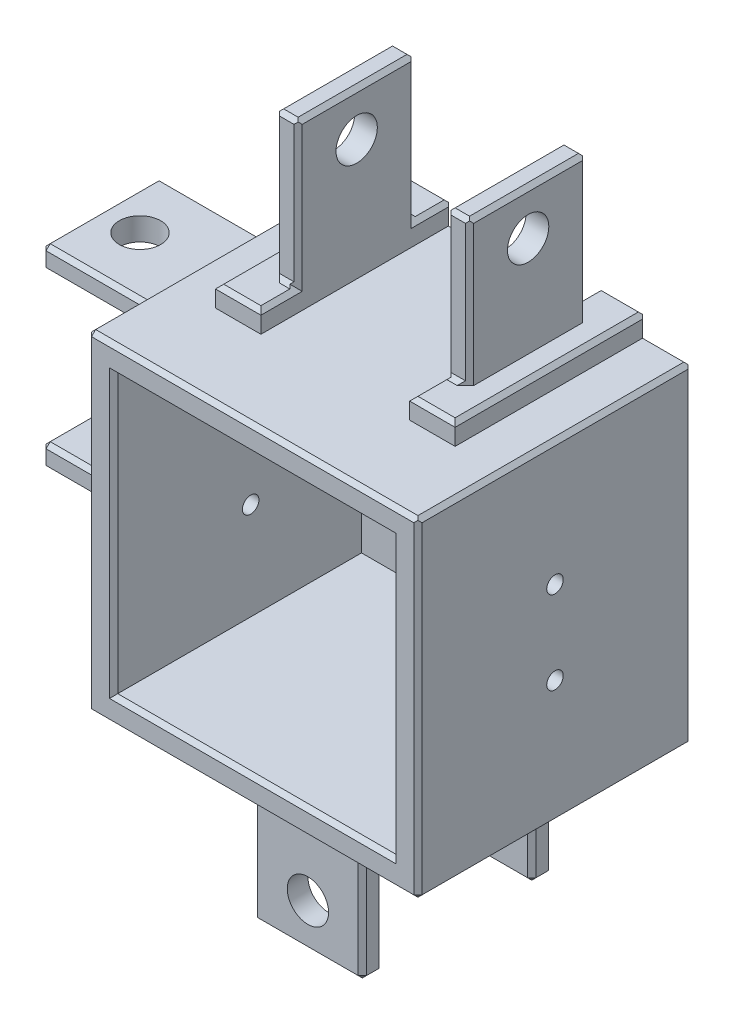
SolidWorks part; units mm, degrees
ref_plane "Alzado" through (0, 0, 0) normal (0, 0, 1) x (1, 0, 0)
ref_plane "Planta" through (0, 0, 0) normal (0, 1, 0) x (1, 0, 0)
ref_plane "Vista lateral" through (0, 0, 0) normal (1, 0, 0) x (0, 0, -1)
sketch "Croquis2" plane through (0, 0, 0) normal (0, 0, 1) x (1, 0, 0)
  line L0 (-30.0752, 21.0526) -> (-30.0752, -58.9474)
  line L1 (-30.0752, -58.9474) -> (49.9248, -58.9474)
  line L2 (49.9248, -58.9474) -> (49.9248, 21.0526)
  line L3 (49.9248, 21.0526) -> (-30.0752, 21.0526)
  dimension "D1" = 80
  dimension "D2" = 80
extrude "Saliente-Extruir1" add sketch "Croquis2" along normal blind 6.35
sketch "Croquis4" plane through (0, 0, 6.35) normal (0, 0, 1) x (1, 0, 0)
  line L0 (-30.0752, 21.0526) -> (49.9248, -58.9474) construction
  line L1 (49.9248, 21.0526) -> (-30.0752, 21.0526) construction
  line L2 (43.5748, -52.5974) -> (-23.7252, -52.5974)
  line L3 (43.5748, -52.5974) -> (43.5748, 14.7026)
  line L4 (43.5748, 14.7026) -> (-23.7252, 14.7026)
  line L5 (-23.7252, -52.5974) -> (-23.7252, 14.7026)
  line L6 (43.5748, -52.5974) -> (-23.7252, 14.7026) construction
  line L7 (43.5748, 14.7026) -> (-23.7252, -52.5974) construction
  line L8 (-30.0752, 21.0526) -> (-30.0752, -58.9474) construction
  line L10 (49.9248, -58.9474) -> (-30.0752, -58.9474)
  line L11 (49.9248, -58.9474) -> (49.9248, 21.0526)
  line L12 (49.9248, 21.0526) -> (-30.0752, 21.0526)
  line L13 (-30.0752, -58.9474) -> (-30.0752, 21.0526)
  line L14 (49.9248, -58.9474) -> (-30.0752, 21.0526) construction
  line L15 (49.9248, 21.0526) -> (-30.0752, -58.9474) construction
  point P4 (9.9248, -18.9474)
  point P13 (9.9248, -18.9474)
  dimension "D1" = 6.35
  dimension "D2" = 6.35
extrude "Saliente-Extruir2" add sketch "Croquis4" along normal blind 60
sketch "Croquis5" plane through (0, 0, 6.35) normal (0, 0, 1) x (1, 0, 0)
  line L0 (-23.7252, -52.5974) -> (43.5748, 14.7026) construction
  line L2 (-23.7252, 14.7026) -> (43.5748, -52.5974) construction
  circle A0 centre (9.9248, -18.9474) radius 30
  dimension "D1" = 60
extrude "Cortar-Extruir1" cut sketch "Croquis5" against normal blind 40
sketch "Croquis6" plane through (0, 21.0526, 0) normal (0, 1, 0) x (1, 0, 0)
  line L28 (27.9248, 0) -> (38.9248, 0)
  line L29 (-13.5752, -9) -> (-13.5752, -37.35)
  line L30 (-8.0752, -37.35) -> (-13.5752, -37.35)
  line L31 (-8.0752, -9) -> (-8.0752, -37.35)
  line L32 (-8.0752, -9) -> (-13.5752, -9)
  line L33 (-19.0752, 0) -> (-19.0752, -46.35)
  line L34 (-8.0752, -46.35) -> (-19.0752, -46.35)
  line L35 (-8.0752, 0) -> (-8.0752, -46.35)
  line L36 (-8.0752, 0) -> (-19.0752, 0)
  line L37 (27.9248, 0) -> (27.9248, -46.35)
  line L38 (27.9248, -46.35) -> (38.9248, -46.35)
  line L39 (38.9248, 0) -> (38.9248, -46.35)
  line L40 (27.9248, -9) -> (33.4248, -9)
  line L41 (27.9248, -9) -> (27.9248, -37.35)
  line L42 (27.9248, -37.35) -> (33.4248, -37.35)
  line L43 (33.4248, -9) -> (33.4248, -37.35)
  line M9 (49.9248, 0) -> (-30.0752, 0)
  line M11 (-30.0752, -66.35) -> (49.9248, -66.35)
extrude "Saliente-Extruir3" add sketch "Croquis6" along normal blind 5 separate body contours L35 L33 L30 L29 L32 M9 M11 | L40 L43 L42 L37 L39 M11 M9
sketch "Croquis8" plane through (0, 21.0526, 0) normal (0, 1, 0) x (1, 0, 0)
  line L20 (9.9248, -66.35) -> (9.9248, -43.312) construction
  line L21 (49.9248, -66.35) -> (-30.0752, -66.35) construction
  line L22 (-8.0752, -37.35) -> (-8.0752, -9)
  line L23 (-13.5752, -37.35) -> (-8.0752, -37.35)
  line L24 (-13.5752, -9) -> (-13.5752, -37.35)
  line L25 (-8.0752, -9) -> (-13.5752, -9)
  line L26 (33.4248, -9) -> (33.4248, -37.35)
  line L27 (33.4248, -37.35) -> (27.9248, -37.35)
  line L28 (27.9248, -37.35) -> (27.9248, -9)
  line L29 (27.9248, -9) -> (33.4248, -9)
extrude "Saliente-Extruir4" add sketch "Croquis8" along normal blind 40
sketch "Croquis9" plane through (-13.5752, 0, 0) normal (-1, 0, 0) x (0, 0, 1)
  circle A0 centre (23.175, 50.3161) radius 5
  dimension "D1" = 10
extrude "Cortar-Extruir2" cut sketch "Croquis9" against normal up to surface (47 mm away) up to face at (33.4248, 43.5526, 23.175)
sketch "Croquis10" plane through (-30.0752, 0, 0) normal (-1, 0, 0) x (0, 0, 1)
  line L5 (37.35, -0.9474) -> (37.35, 4.5526)
  line L14 (9, 4.5526) -> (37.35, 4.5526)
  line L15 (9, -0.9474) -> (9, 4.5526)
  line L24 (9, -0.9474) -> (37.35, -0.9474)
  line L25 (46.35, -0.9474) -> (46.35, 10.0526)
  line L26 (0, -0.9474) -> (46.35, -0.9474)
  line L27 (0, 10.0526) -> (0, -0.9474)
  line L28 (0, 10.0526) -> (46.35, 10.0526)
  line L30 (0, -47.9474) -> (46.35, -47.9474)
  line L31 (0, -47.9474) -> (0, -36.9474)
  line L32 (0, -36.9474) -> (46.35, -36.9474)
  line L33 (46.35, -36.9474) -> (46.35, -47.9474)
  line L34 (9, -36.9474) -> (37.35, -36.9474)
  line L35 (9, -36.9474) -> (9, -42.4474)
  line L36 (9, -42.4474) -> (37.35, -42.4474)
  line L37 (37.35, -36.9474) -> (37.35, -42.4474)
  line M12 (0, 21.0526) -> (0, -58.9474)
extrude "Saliente-Extruir5" add sketch "Croquis10" along normal blind 5 contours L28 L26 L15 L14 L5 L25 M12 | L32 L37 L36 L35 L30 L33 M12
sketch "Croquis11" plane through (-30.0752, 0, 0) normal (-1, 0, 0) x (0, 0, 1)
  line L0 (9, 4.5526) -> (9, -0.9474)
  line L9 (9, -0.9474) -> (37.35, -0.9474)
  line L12 (9, -36.9474) -> (9, -42.4474)
  line L15 (37.35, -36.9474) -> (9, -36.9474)
  line L16 (37.35, -36.9474) -> (37.35, -42.4474)
  line L17 (37.35, -42.4474) -> (9, -42.4474)
  line L18 (9, 4.5526) -> (37.35, 4.5526)
  line L19 (37.35, 4.5526) -> (37.35, -0.9474)
extrude "Saliente-Extruir6" add sketch "Croquis11" along normal blind 40
sketch "Croquis12" plane through (0, 4.5526, 0) normal (0, 1, 0) x (1, 0, 0)
  circle A0 centre (-60.519, -23.175) radius 5
  dimension "D1" = 10
extrude "Cortar-Extruir3" cut sketch "Croquis12" against normal up to surface (47 mm away) up to face at (-52.5752, -42.4474, 23.175)
sketch "Croquis13" plane through (0, -58.9474, 0) normal (0, -1, 0) x (1, 0, 0)
  line L5 (-16.2258, 9) -> (-16.2258, 2)
  line L12 (-16.2258, 9) -> (30.1242, 9)
  line L13 (-16.2258, 2) -> (30.1242, 2)
  line L14 (30.1242, 2) -> (30.1242, 9)
  line L16 (-16.2258, 45) -> (30.1242, 45)
  line L17 (30.1242, 45) -> (30.1242, 52)
  line L18 (-16.2258, 45) -> (-16.2258, 52)
  line L19 (-16.2258, 52) -> (30.1242, 52)
extrude "Saliente-Extruir7" add sketch "Croquis13" along normal blind 5 contours L18 L19 L17 L16 | L14 L12 L5 L13
sketch "Croquis14" plane through (0, -58.9474, 0) normal (0, -1, 0) x (1, 0, 0)
  line L14 (-6.2258, 45) -> (20.1242, 45)
  line L15 (-16.2258, 45) -> (30.1242, 45) construction
  line L16 (20.1242, 45) -> (20.1242, 50)
  line L17 (20.1242, 50) -> (-6.2258, 50)
  line L18 (-6.2258, 50) -> (-6.2258, 45)
  line L19 (-6.2258, 9) -> (20.1242, 9)
  line L20 (-16.2258, 9) -> (30.1242, 9) construction
  line L21 (20.1242, 9) -> (20.1242, 4)
  line L22 (20.1242, 4) -> (-6.2258, 4)
  line L23 (-6.2258, 4) -> (-6.2258, 9)
extrude "Saliente-Extruir8" add sketch "Croquis14" along normal blind 40
sketch "Croquis15" plane through (0, 0, 4) normal (0, 0, -1) x (-1, 0, 0)
  circle A0 centre (-6.9492, -88.3111) radius 5
  dimension "D1" = 10
extrude "Cortar-Extruir4" cut sketch "Croquis15" against normal blind 70
sketch "Croquis16" plane through (49.9248, 0, 0) normal (1, 0, 0) x (0, 0, -1)
  line L0 (-66.35, 21.0526) -> (0, -58.9474) construction
  line L1 (-66.35, -58.9474) -> (0, 21.0526) construction
  line L2 (-33.175, -18.9474) -> (-33.175, -8.9474) construction
  line L3 (-33.175, -18.9474) -> (-33.175, -29.0664) construction
  circle A0 centre (-33.175, -29.0664) radius 2
  circle A1 centre (-33.175, -8.9474) radius 2
  dimension "D2" = 4
  dimension "D3" = 4
  dimension "D1" = 10
extrude "Cortar-Extruir5" cut sketch "Croquis16" against normal up to surface (80 mm away) up to face at (-30.0752, -18.9474, 26.5083)
chamfer "Chaflán1" distance 1 angle 45 27 edges at (-30.0752, -18.9474, 66.35) (-30.0752, 15.5526, 0) (9.9248, 21.0526, 66.35) (44.4248, 21.0526, 0) (49.9248, -18.9474, 0) (49.9248, -18.9474, 66.35) (9.9248, -58.9474, 0) (9.9248, -58.9474, 66.35) (-30.0752, -58.9474, 33.175) (-30.0752, 21.0526, 33.175) (49.9248, -58.9474, 33.175) (-32.5752, 10.0526, 0) (-32.5752, -0.9474, 0) (-30.0752, -18.9474, 0) (-32.5752, -36.9474, 0) (-32.5752, -47.9474, 0) (38.9248, 23.5526, 0) (27.9248, 23.5526, 0) (9.9248, 21.0526, 0) (-8.0752, 23.5526, 0) (-13.5752, 26.0526, 0) (-19.0752, 23.5526, 0) (33.4248, 26.0526, 0) (-24.5752, 21.0526, 0) (-35.0752, 4.5526, 0) (-35.0752, -42.4474, 0) (-30.0752, -53.4474, 0)
chamfer "Chaflán2" distance 1 angle 45 5 edges at (49.9248, 21.0526, 33.175) (-23.7252, -18.9474, 66.35) (9.9248, -52.5974, 66.35) (43.5748, -18.9474, 66.35) (9.9248, 14.7026, 66.35)
ref_plane "Plano2" through (-8.0752, 21.0526, 1) normal (0, 0, 1) x (1, 0, 0)
chamfer "Chaflán9" distance 1 angle 45 4 edges at (-13.5752, 61.0526, 23.175) (-10.8252, 61.0526, 9) (-8.0752, 61.0526, 23.175) (-10.8252, 61.0526, 37.35)
chamfer "Chaflán10" distance 1 angle 45 4 edges at (33.4248, 61.0526, 23.175) (30.6748, 61.0526, 37.35) (27.9248, 61.0526, 23.175) (30.6748, 61.0526, 9)
chamfer "Chaflán11" distance 1 angle 45 16 edges at (33.4248, 43.0526, 37.35) (-13.5752, 43.0526, 37.35) (33.4248, 43.0526, 9) (-13.5752, 43.0526, 9) (-8.0752, 43.0526, 9) (-8.0752, 26.0526, 5) (-8.0752, 43.0526, 37.35) (-19.0752, 26.0526, 23.675) (-13.5752, 26.0526, 46.35) (-8.0752, 26.0526, 41.85) (27.9248, 43.0526, 9) (27.9248, 26.0526, 5) (27.9248, 43.0526, 37.35) (27.9248, 26.0526, 41.85) (38.9248, 26.0526, 23.675) (33.4248, 26.0526, 46.35)
chamfer "Chaflán12" distance 1 angle 45 24 edges at (-70.0752, -42.4474, 23.175) (-52.5752, -42.4474, 9) (-70.0752, -39.6974, 9) (-35.0752, -36.9474, 5) (-52.5752, -36.9474, 9) (-70.0752, -36.9474, 23.175) (-52.5752, -42.4474, 37.35) (-70.0752, -39.6974, 37.35) (-52.5752, -36.9474, 37.35) (-35.0752, -47.9474, 23.675) (-35.0752, -42.4474, 46.35) (-35.0752, -36.9474, 41.85) (-35.0752, -0.9474, 5) (-52.5752, -0.9474, 9) (-52.5752, 4.5526, 9) (-52.5752, 4.5526, 37.35) (-70.0752, -0.9474, 23.175) (-70.0752, 1.8026, 9) (-70.0752, 4.5526, 23.175) (-70.0752, 1.8026, 37.35) (-52.5752, -0.9474, 37.35) (-35.0752, -0.9474, 41.85) (-35.0752, 10.0526, 23.675) (-35.0752, 4.5526, 46.35)
chamfer "Chaflán13" distance 1 angle 45 32 edges at (25.1242, -63.9474, 9) (30.1242, -63.9474, 5.5) (6.9492, -63.9474, 2) (-16.2258, -63.9474, 5.5) (-11.2258, -63.9474, 9) (6.9492, -63.9474, 4) (-6.2258, -81.4474, 9) (-6.2258, -63.9474, 6.5) (-6.2258, -81.4474, 4) (6.9492, -98.9474, 9) (-6.2258, -98.9474, 6.5) (6.9492, -98.9474, 4) (20.1242, -81.4474, 4) (20.1242, -98.9474, 6.5) (20.1242, -81.4474, 9) (20.1242, -63.9474, 6.5) (6.9492, -63.9474, 50) (20.1242, -81.4474, 45) (20.1242, -81.4474, 50) (20.1242, -63.9474, 47.5) (-6.2258, -81.4474, 50) (6.9492, -98.9474, 50) (20.1242, -98.9474, 47.5) (6.9492, -98.9474, 45) (-6.2258, -98.9474, 47.5) (-6.2258, -81.4474, 45) (-6.2258, -63.9474, 47.5) (-11.2258, -63.9474, 45) (25.1242, -63.9474, 45) (30.1242, -63.9474, 48.5) (-16.2258, -63.9474, 48.5) (6.9492, -63.9474, 52)
chamfer "Chaflán14" distance 1 angle 45 8 edges at (-10.8252, 26.0526, 9) (30.6748, 26.0526, 9) (-10.8252, 26.0526, 37.35) (30.6748, 26.0526, 37.35) (-35.0752, 1.8026, 37.35) (-35.0752, 1.8026, 9) (-35.0752, -39.6974, 9) (-35.0752, -39.6974, 37.35)
chamfer "Chaflán15" distance 1 angle 45 2 edges at (39.9248, -18.9474, 6.35) (39.9248, -18.9474, 0)
